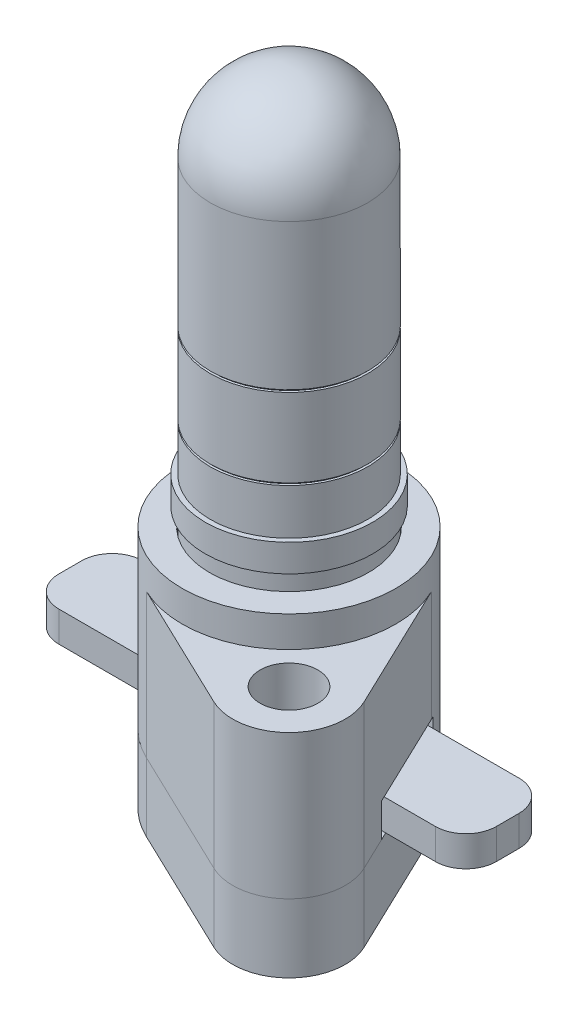
SolidWorks part; units mm, degrees
ref_plane "Front Plane" through (0, 0, 0) normal (0, 0, 1) x (1, 0, 0)
ref_plane "Top Plane" through (0, 0, 0) normal (0, 1, 0) x (1, 0, 0)
ref_plane "Right Plane" through (0, 0, 0) normal (1, 0, 0) x (0, 0, -1)
sketch "Sketch1" plane through (0, 0, 0) normal (0, 1, 0) x (1, 0, 0)
  circle A0 centre (0, 0) radius 1.75
  circle A1 centre (0, 0) radius 15
  dimension "D1" = 3.5
  dimension "D2" = 30
extrude "Boss-Extrude1" add sketch "Sketch1" against normal blind 4.5
sketch "Sketch2" plane through (0, 0, 0) normal (0, 1, 0) x (1, 0, 0)
  line L0 (0, 0) -> (-7.0711, 7.0711) construction
  line L1 (0, 0) -> (-13.4225, 0) construction
  line L2 (0, 0) -> (4.1472, 4.1472) construction
  line L3 (-10.4084, 5.4735) -> (-6.3365, -3.0331)
  line L4 (-5.4735, 10.4084) -> (3.0331, 6.3365)
  line L5 (5.4735, -10.4084) -> (-3.0331, -6.3365)
  line L6 (10.4084, -5.4735) -> (6.3365, 3.0331)
  circle A0 centre (0, 0) radius 5.225
  arc A1 (-6.3365, -3.0331) -> (-3.0331, -6.3365) centre (0, 0) ccw
  circle A2 centre (-7.0711, 7.0711) radius 1.9
  arc A3 (-5.4735, 10.4084) -> (-10.4084, 5.4735) centre (-7.0711, 7.0711) ccw
  circle A4 centre (7.0711, -7.0711) radius 1.9
  arc A5 (10.4084, -5.4735) -> (5.4735, -10.4084) centre (7.0711, -7.0711) cw
  arc A6 (6.3365, 3.0331) -> (3.0331, 6.3365) centre (0, 0) ccw
  arc A7 (-10.4084, 5.4735) -> (-6.0888, 3.5038) centre (-7.0711, 7.0711) ccw construction
  arc A8 (-6.0888, 3.5038) -> (-7.025, 0) centre (0, 0) ccw construction
  arc A9 (-7.025, 0) -> (-6.3365, -3.0331) centre (0, 0) ccw construction
  arc A10 (-3.0331, -6.3365) -> (3.5038, -6.0888) centre (0, 0) ccw construction
  arc A11 (5.4735, -10.4084) -> (3.5038, -6.0888) centre (7.0711, -7.0711) cw construction
  arc A12 (6.0888, -3.5038) -> (6.3365, 3.0331) centre (0, 0) ccw construction
  arc A13 (6.0888, -3.5038) -> (10.4084, -5.4735) centre (7.0711, -7.0711) cw construction
  arc A14 (3.0331, 6.3365) -> (-3.5038, 6.0888) centre (0, 0) ccw construction
  arc A15 (-3.5038, 6.0888) -> (-5.4735, 10.4084) centre (-7.0711, 7.0711) ccw construction
  dimension "D1" = 10.45
  dimension "D2" = 14.05
  dimension "D4" = 3.8
  dimension "D5" = 7.4
  dimension "D3" = 45
  dimension "D6" = 10
extrude "Boss-Extrude2" add sketch "Sketch2" along normal blind 11.5 separate body
sketch "Sketch3" plane through (0, 11.5, 0) normal (0, 1, 0) x (1, 0, 0)
  line L1 (15.5997, -13.4039) -> (-15.5997, -13.4039)
  line L2 (15.5997, -13.4039) -> (15.5997, 13.4039)
  line L3 (15.5997, 13.4039) -> (-15.5997, 13.4039)
  line L4 (-15.5997, -13.4039) -> (-15.5997, 13.4039)
  line L5 (15.5997, -13.4039) -> (-15.5997, 13.4039) construction
  line L6 (15.5997, 13.4039) -> (-15.5997, -13.4039) construction
  circle A0 centre (0, 0) radius 7.025
extrude "Cut-Extrude1" cut sketch "Sketch3" against normal blind 2.03
sketch "Sketch4" plane through (0, 0, 0) normal (1, 0, 0) x (0, 0, -1)
  line L0 (0, 0) -> (-3.0331, 0) construction
  line L1 (-3.25, 0) -> (3.25, 0)
  line L2 (-3.25, 0) -> (-3.25, 2.2)
  line L3 (-3.25, 2.2) -> (3.25, 2.2)
  line L4 (3.25, 0) -> (3.25, 2.2)
  line L5 (0, 2.2) -> (0, 0) construction
  dimension "D1" = 6.5
  dimension "D2" = 2.2
extrude "Cut-Extrude2" cut sketch "Sketch4" against normal through all both and the other way through all
sketch "Sketch5" plane through (0, 0, 0) normal (0, 1, 0) x (1, 0, 0)
  line L0 (-10.4084, 5.4735) -> (-6.3365, -3.0331) construction
  line L1 (5.4735, -10.4084) -> (-3.0331, -6.3365) construction
  line L2 (10.4084, -5.4735) -> (6.3365, 3.0331) construction
  line L3 (-5.4735, 10.4084) -> (3.0331, 6.3365) construction
  line L4 (-10.4084, 5.4735) -> (-6.3365, -3.0331)
  line L5 (5.4735, -10.4084) -> (-3.0331, -6.3365)
  line L6 (10.4084, -5.4735) -> (6.3365, 3.0331)
  line L7 (-5.4735, 10.4084) -> (3.0331, 6.3365)
  circle A0 centre (7.0711, -7.0711) radius 1.9 construction
  circle A1 centre (-7.0711, 7.0711) radius 1.9 construction
  arc A2 (-5.4735, 10.4084) -> (-10.4084, 5.4735) centre (-7.0711, 7.0711) ccw construction
  arc A3 (-6.3365, -3.0331) -> (-3.0331, -6.3365) centre (0, 0) ccw construction
  arc A4 (5.4735, -10.4084) -> (10.4084, -5.4735) centre (7.0711, -7.0711) ccw construction
  arc A5 (6.3365, 3.0331) -> (3.0331, 6.3365) centre (0, 0) ccw construction
  circle A6 centre (7.0711, -7.0711) radius 1.9 construction
  circle A7 centre (-7.0711, 7.0711) radius 1.9 construction
  arc A8 (-5.4735, 10.4084) -> (-10.4084, 5.4735) centre (-7.0711, 7.0711) ccw
  arc A9 (-6.3365, -3.0331) -> (-3.0331, -6.3365) centre (0, 0) ccw
  arc A10 (5.4735, -10.4084) -> (10.4084, -5.4735) centre (7.0711, -7.0711) ccw
  arc A11 (6.3365, 3.0331) -> (3.0331, 6.3365) centre (0, 0) ccw
  circle A12 centre (7.0711, -7.0711) radius 1.4
  circle A13 centre (-7.0711, 7.0711) radius 1.4
  circle A14 centre (0, 0) radius 15
  circle A15 centre (0, 0) radius 15 construction
  circle M15 centre (0, 0) radius 15
  dimension "D1" = 2.8
extrude "Cut-Extrude4" cut sketch "Sketch5" against normal through all contours A13 | A12 | A11 L6 A10 L5 A9 L4 A8 L7 M15 region at (7.0711, 0, 7.0711) region at (-7.0711, 0, -7.0711) region at (-14.5757, 0, 0)
sketch "Sketch8" plane through (0, 0, 0) normal (1, 0, 0) x (0, 0, -1)
  line L0 (0, 0) -> (0, -10.1896) construction
  line L1 (0, 32.525) -> (0, 37.7)
  line L2 (0, 0) -> (-5.175, 0)
  line L3 (0, 0) -> (0, 32.525)
  line L4 (0, 32.525) -> (-5.175, 32.525) construction
  line L5 (-5.175, 0) -> (-5.175, 12.7)
  line L6 (-5.175, 14.5) -> (-5.5, 14.5)
  line L7 (-5.175, 14.5) -> (-5.175, 12.7) construction
  line L8 (-5.175, 12.7) -> (-5.5, 12.7)
  line L9 (-5.5, 14.5) -> (-5.5, 12.7)
  line L10 (-5.175, 14.5) -> (-5.175, 17.5)
  line L11 (-5.175, 12.7) -> (-5.175, 14.5) construction
  line L12 (7.025, 11.5) -> (-7.025, 11.5) construction
  line L13 (-5.175, 17.5) -> (-5.025, 17.5)
  line L14 (-5.175, 22.8) -> (-5.025, 22.8)
  line L15 (-5.175, 22.95) -> (-5.025, 22.8)
  line L16 (-5.175, 17.65) -> (-5.025, 17.5)
  line L17 (-5.025, 17.5) -> (0, 17.5) construction
  line L18 (-5.175, 17.65) -> (-5.175, 22.8)
  line L19 (-5.175, 17.5) -> (-5.175, 17.65) construction
  line L20 (-5.025, 22.8) -> (0, 22.8) construction
  line L21 (-5.175, 22.95) -> (-5.175, 32.525)
  line L22 (-5.175, 22.8) -> (-5.175, 22.95) construction
  arc A0 (0, 37.7) -> (-5.175, 32.525) centre (0, 32.525) ccw
  arc A1 (0, 27.35) -> (0, 37.7) centre (0, 32.525) ccw construction
  arc A2 (-5.175, 32.525) -> (0, 27.35) centre (0, 32.525) ccw construction
  dimension "D1" = 5.175
  dimension "D2" = 11
  dimension "D3" = 3
  dimension "D4" = 1.8
  dimension "D5" = 26.2
  dimension "D6" = 6
  dimension "D7" = 11.3
  dimension "D8" = 0.15
  dimension "D9" = 45
revolve "Revolve1" add sketch "Sketch8" angle 360 about L0
sketch "Sketch9" plane through (0, 0, 0) normal (0, 1, 0) x (1, 0, 0)
  line L0 (0, 0) -> (-8.375, 0) construction
  line L1 (0, 0) -> (0, 12.0634) construction
  line L2 (-12.375, -2.75) -> (-2.375, -2.75)
  line L3 (-14.375, -0.75) -> (-14.375, 0.75)
  line L4 (-12.375, 2.75) -> (-2.375, 2.75)
  line L5 (-2.375, -2.75) -> (-2.375, 2.75)
  line L6 (-14.375, -2.75) -> (-2.375, 2.75) construction
  line L7 (-14.375, 2.75) -> (-2.375, -2.75) construction
  line L8 (14.375, 2.75) -> (2.375, -2.75) construction
  line L9 (14.375, -2.75) -> (2.375, 2.75) construction
  line L10 (2.375, -2.75) -> (2.375, 2.75)
  line L11 (12.375, 2.75) -> (2.375, 2.75)
  line L12 (14.375, -0.75) -> (14.375, 0.75)
  line L13 (12.375, -2.75) -> (2.375, -2.75)
  arc A0 (-12.375, -2.75) -> (-14.375, -0.75) centre (-12.375, -0.75) cw
  arc A1 (-14.375, 0.75) -> (-12.375, 2.75) centre (-12.375, 0.75) cw
  arc A2 (14.375, 0.75) -> (12.375, 2.75) centre (12.375, 0.75) ccw
  arc A3 (12.375, -2.75) -> (14.375, -0.75) centre (12.375, -0.75) ccw
  dimension "D4" = 2
  dimension "D1" = 28.75
  dimension "D2" = 5.5
  dimension "D3" = 12
extrude "Boss-Extrude3" add sketch "Sketch9" along normal blind 2
ref_axis "Axis1" through (0, 22.95, 0) along (0, 1, 0)
ref_plane "Screw_Plane1" through (0, 0, 0) normal (0.7071, 0, -0.7071) x (0, 1, 0)
ref_plane "Screw_Middle" through (0, 0, 0) normal (-0.7071, 0, -0.7071) x (0, 1, 0)
equation "\"D2@Sketch2\"=\"D1@Sketch2\"+.6*3*2"
equation "\"D5@Sketch2\"=\"D4@Sketch2\"+.6*3*2"
